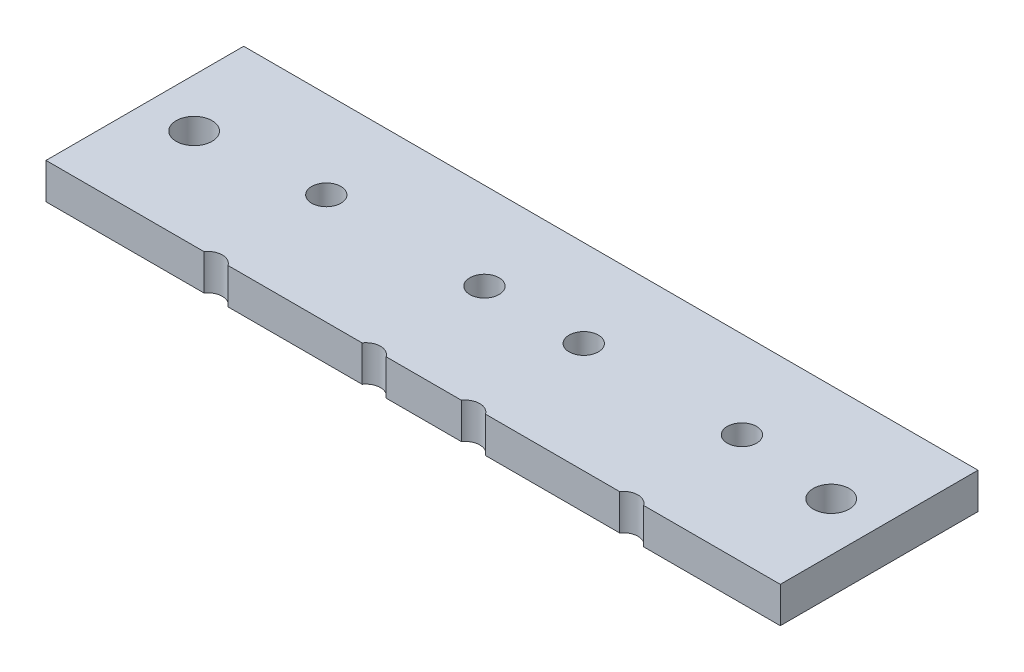
SolidWorks part; units mm, degrees
material "Alumina"
ref_plane "Front Plane" through (0, 0, 0) normal (0, 0, 1) x (1, 0, 0)
ref_plane "Top Plane" through (0, 0, 0) normal (0, 1, 0) x (1, 0, 0)
ref_plane "Right Plane" through (0, 0, 0) normal (1, 0, 0) x (0, 0, -1)
sketch "Sketch1" plane through (0, 0, 0) normal (0, 1, 0) x (1, 0, 0)
  line L1 (0, 0) -> (130, 0)
  line L2 (0, 0) -> (0, -35)
  line L3 (0, -35) -> (130, -35)
  line L4 (130, 0) -> (130, -35)
  dimension "D1" = 130
  dimension "D2" = 35
extrude "Boss-Extrude1" add sketch "Sketch1" along normal blind 6.35
sketch "Sketch5" plane through (0, 6.35, 0) normal (0, 1, 0) x (1, 0, 0)
  line L1 (0, 0) -> (0, -35) construction
  line L2 (130, -35) -> (130, 0) construction
  circle A0 centre (8.605, -17.3826) radius 3.18
  circle A2 centre (121.395, -17.3826) radius 3.18
  dimension "D1" = 8.605
  dimension "D2" = 8.605
extrude "Cut-Extrude2" cut sketch "Sketch5" against normal through all
sketch "Sketch8" plane through (0, 0, 0) normal (0, -1, 0) x (1, 0, 0)
  circle A16 centre (30.0925, 15.4703) radius 2.5866 construction
  circle A17 centre (30.0925, 36.4703) radius 2.5866 construction
  circle A18 centre (58.0925, 36.4703) radius 2.5866 construction
  circle A19 centre (58.0925, 15.4703) radius 2.5866 construction
  circle A20 centre (75.6745, 15.4703) radius 2.5866 construction
  circle A21 centre (75.6745, 36.4703) radius 2.5866 construction
  circle A22 centre (103.6745, 15.4703) radius 2.5866 construction
  circle A23 centre (103.6745, 36.4703) radius 2.5866 construction
  circle A24 centre (30.0925, 15.4703) radius 2.5866
  circle A25 centre (30.0925, 36.4703) radius 2.5866
  circle A26 centre (58.0925, 36.4703) radius 2.5866
  circle A27 centre (58.0925, 15.4703) radius 2.5866
  circle A28 centre (75.6745, 15.4703) radius 2.5866
  circle A29 centre (75.6745, 36.4703) radius 2.5866
  circle A30 centre (103.6745, 15.4703) radius 2.5866
  circle A31 centre (103.6745, 36.4703) radius 2.5866
extrude "Cut-Extrude4" cut sketch "Sketch8" against normal through all
